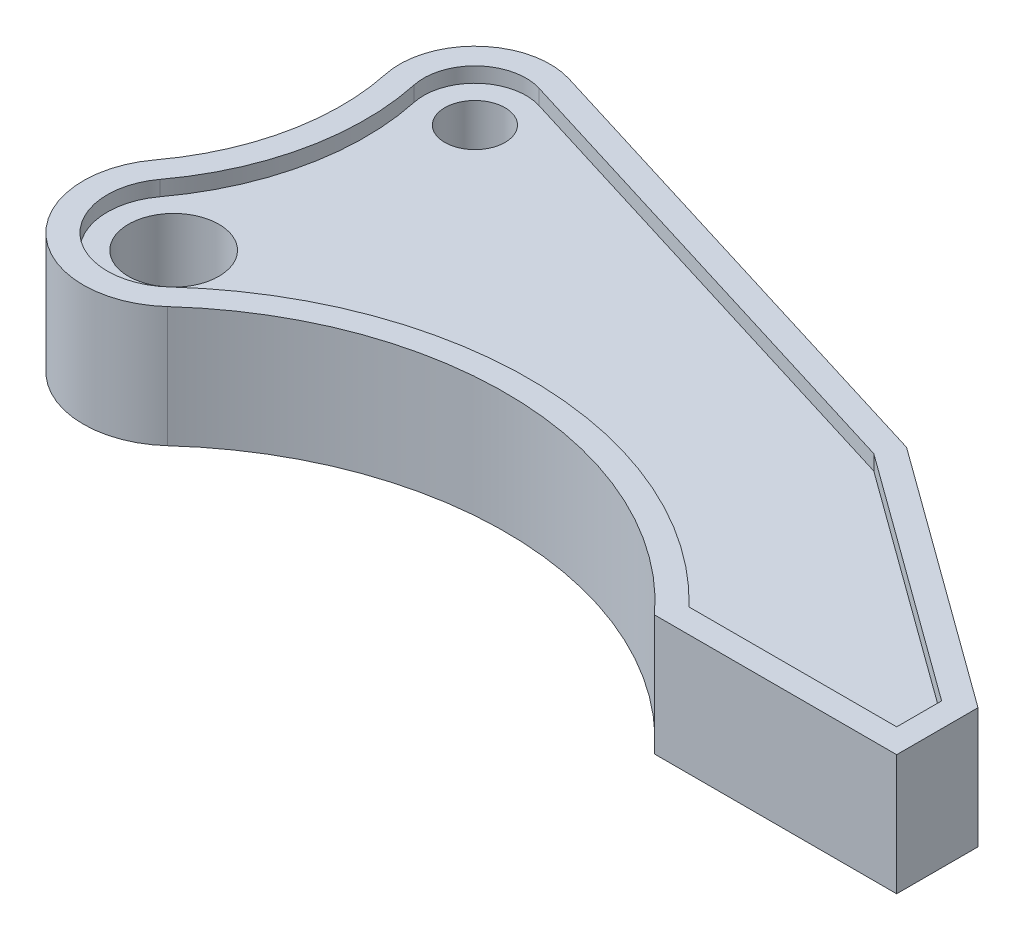
SolidWorks part; units mm, degrees
ref_plane "Front Plane" through (0, 0, 0) normal (0, 0, 1) x (1, 0, 0)
ref_plane "Top Plane" through (0, 0, 0) normal (0, 1, 0) x (1, 0, 0)
ref_plane "Right Plane" through (0, 0, 0) normal (1, 0, 0) x (0, 0, -1)
sketch "Sketch1" plane through (0, 0, 0) normal (0, 1, 0) x (1, 0, 0)
  line L0 (0, 0) -> (0, 535.1459) construction
  line L1 (21.3613, 109.8917) -> (183.2879, 60)
  line L2 (183.2879, 60) -> (270, -3)
  line L3 (270, -3) -> (270, -30)
  line L4 (270, -30) -> (189.6287, -30)
  arc A0 (-24.0853, 17.8857) -> (20.2, -22.1802) centre (0, 0) ccw
  arc A1 (21.3613, 109.8917) -> (-10.4435, 80.7545) centre (14, 86) ccw
  arc A2 (-10.4435, 80.7545) -> (-24.0853, 17.8857) centre (-86.7072, 64.3884) cw
  arc A3 (20.2, -22.1802) -> (189.6287, -30) centre (101, -110.9009) cw
  point P21 (-10.4811, 47.8482)
  dimension "D1" = 60
  dimension "D2" = 50
  dimension "D7" = 270
  dimension "D11" = 120
  dimension "D3" = 14
  dimension "D4" = 86
  dimension "D5" = 27
  dimension "D6" = 36
  dimension "D8" = 101
  dimension "D9" = 90
  dimension "D10" = 78
extrude "Boss-Extrude1" add sketch "Sketch1" along normal mid plane 30
sketch "Sketch2" plane through (0, 0, 0) normal (0, 1, 0) x (1, 0, 0)
  line L8 (193.0904, -22) -> (262, -22)
  line L9 (262, -22) -> (262, -7.0762)
  line L10 (262, -7.0762) -> (179.6615, 52.7462)
  line L11 (179.6615, 52.7462) -> (19.0057, 102.2463)
  line L12 (193.0904, -22) -> (262, -22)
  line L13 (262, -22) -> (262, -7.0762)
  line L14 (262, -7.0762) -> (179.6615, 52.7462)
  line L15 (179.6615, 52.7462) -> (19.0057, 102.2463)
  line L16 (189.6287, -30) -> (270, -30)
  line L17 (270, -30) -> (270, -3)
  line L18 (270, -3) -> (183.2879, 60)
  line L19 (183.2879, 60) -> (21.3613, 109.8917)
  line L20 (189.6287, -30) -> (270, -30)
  line L21 (270, -30) -> (270, -3)
  line L22 (270, -3) -> (183.2879, 60)
  line L23 (183.2879, 60) -> (21.3613, 109.8917)
  arc A8 (19.0057, 102.2463) -> (-2.6216, 82.433) centre (14, 86) ccw
  arc A9 (-17.6626, 13.1162) -> (-2.6216, 82.433) centre (-86.7072, 64.3884) ccw
  arc A10 (-17.6626, 13.1162) -> (14.8133, -16.2655) centre (0, 0) ccw
  arc A11 (193.0904, -22) -> (14.8133, -16.2655) centre (101, -110.9009) ccw
  arc A12 (19.0057, 102.2463) -> (-2.6216, 82.433) centre (14, 86) ccw
  arc A13 (-17.6626, 13.1162) -> (-2.6216, 82.433) centre (-86.7072, 64.3884) ccw
  arc A14 (-17.6626, 13.1162) -> (14.8133, -16.2655) centre (0, 0) ccw
  arc A15 (193.0904, -22) -> (14.8133, -16.2655) centre (101, -110.9009) ccw
  arc A16 (21.3613, 109.8917) -> (-10.4435, 80.7545) centre (14, 86) ccw
  arc A17 (-24.0853, 17.8857) -> (-10.4435, 80.7545) centre (-86.7072, 64.3884) ccw
  arc A18 (-24.0853, 17.8857) -> (20.2, -22.1802) centre (0, 0) ccw
  arc A19 (189.6287, -30) -> (20.2, -22.1802) centre (101, -110.9009) ccw
  arc A20 (21.3613, 109.8917) -> (-10.4435, 80.7545) centre (14, 86) ccw
  arc A21 (-24.0853, 17.8857) -> (-10.4435, 80.7545) centre (-86.7072, 64.3884) ccw
  arc A22 (-24.0853, 17.8857) -> (20.2, -22.1802) centre (0, 0) ccw
  arc A23 (189.6287, -30) -> (20.2, -22.1802) centre (101, -110.9009) ccw
  dimension "D1" = 8
  dimension "D2" = 0
extrude "Boss-Extrude2" add sketch "Sketch2" along normal mid plane 40
sketch "Sketch5" plane through (0, 15, 0) normal (0, 1, 0) x (1, 0, 0)
  circle A0 centre (0, 0) radius 15
  circle A1 centre (14, 86) radius 10
  dimension "D1" = 30
  dimension "D2" = 20
  dimension "D4" = 14
  dimension "D3" = 86
extrude "Cut-Extrude1" cut sketch "Sketch5" against normal blind 30
